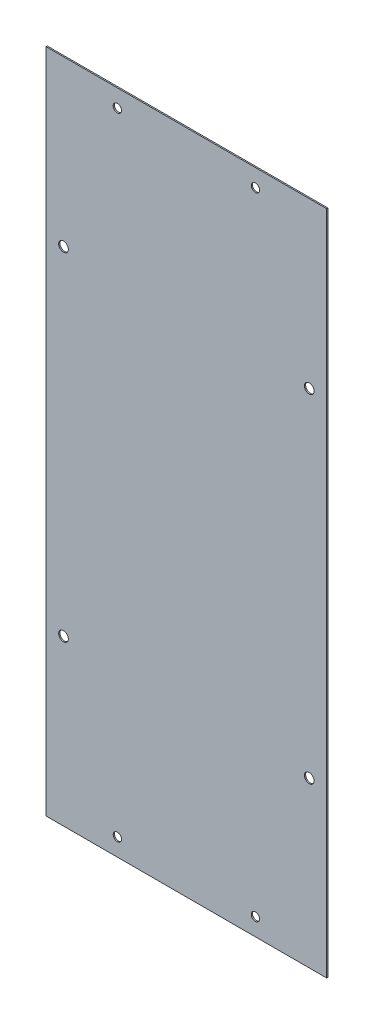
SolidWorks part; units mm, degrees
ref_plane "前视基准面" through (0, 0, 0) normal (0, 0, 1) x (1, 0, 0)
ref_plane "上视基准面" through (0, 0, 0) normal (0, 1, 0) x (1, 0, 0)
ref_plane "右视基准面" through (0, 0, 0) normal (1, 0, 0) x (0, 0, -1)
sketch "草图1" plane through (0, 0, 0) normal (0, 0, 1) x (1, 0, 0)
  line L1 (-101.6, 241.3) -> (101.6, 241.3)
  line L2 (-101.6, 241.3) -> (-101.6, -241.3)
  line L3 (-101.6, -241.3) -> (101.6, -241.3)
  line L4 (101.6, 241.3) -> (101.6, -241.3)
  line L5 (-101.6, 241.3) -> (101.6, -241.3) construction
  line L6 (-101.6, -241.3) -> (101.6, 241.3) construction
  point P0 (0, 0)
  dimension "D1" = 203.2
  dimension "D2" = 482.6
extrude "凸台-拉伸1" add sketch "草图1" along normal blind 0.9
sketch "草图2" plane through (0, 0, 0.9) normal (0, 0, 1) x (1, 0, 0)
  line L2 (-89, 122.2) -> (89, 122.2) construction
  line L5 (-89, 122.2) -> (-89, -122.2) construction
  line L6 (0, 0) -> (50, 0) construction
  line L7 (0, 0) -> (0, 51.14) construction
  line L8 (0, 0) -> (0, 228.6) construction
  line L9 (0, 228.6) -> (50, 228.6) construction
  circle A0 centre (-89, 122.2) radius 3.5
  circle A1 centre (89, 122.2) radius 3.5
  circle A2 centre (89, -122.2) radius 3.5
  circle A3 centre (-89, -122.2) radius 3.5
  circle A4 centre (50, 228.6) radius 3
  circle A5 centre (50, -228.6) radius 3
  circle A6 centre (-50, 228.6) radius 3
  circle A7 centre (-50, -228.6) radius 3
  point P18 (0, 0)
  dimension "D1" = 122.2
  dimension "D2" = 228.6
  dimension "D4" = 50
  dimension "D3" = 178
extrude "切除-拉伸1" cut sketch "草图2" against normal blind 10
